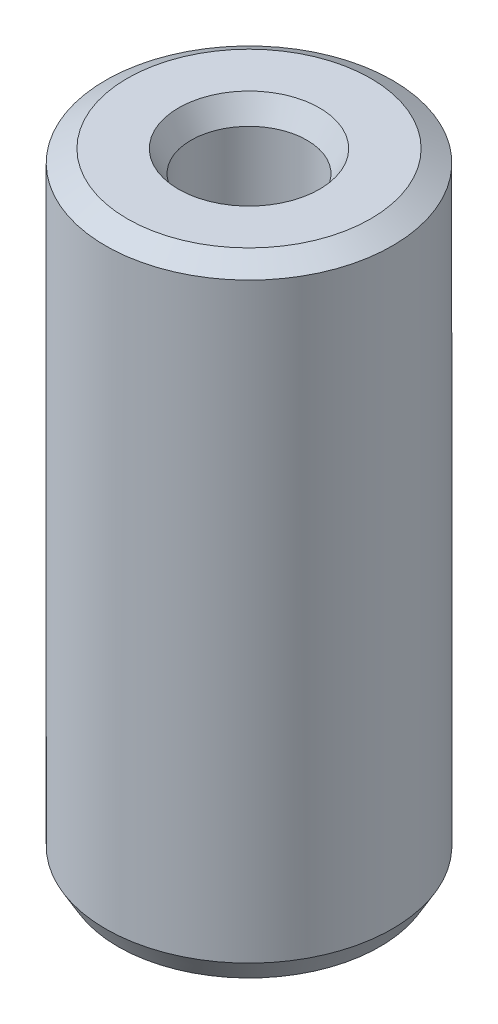
SolidWorks part; units mm, degrees
ref_plane "Front Plane" through (0, 0, 0) normal (0, 0, 1) x (1, 0, 0)
ref_plane "Top Plane" through (0, 0, 0) normal (0, 1, 0) x (1, 0, 0)
ref_plane "Right Plane" through (0, 0, 0) normal (1, 0, 0) x (0, 0, -1)
sketch "Sketch1" plane through (0, 0, 0) normal (0, 1, 0) x (1, 0, 0)
  circle A0 centre (0, 0) radius 45
  dimension "SLEEVE_OD" = 90
extrude "Boss-Extrude1" add sketch "Sketch1" along normal blind 196.344
sketch "Sketch2" plane through (0, 0, 0) normal (0, 1, 0) x (1, 0, 0)
  circle A0 centre (0, 0) radius 18.1924
  dimension "BORE_D" = 36.3849
extrude "Cut-Extrude1" cut sketch "Sketch2" along normal through all
chamfer "Chamfer1" distance 3.9336 angle 60 4 edges at (0, 196.344, 18.1924) (0, 0, 18.1924) (0, 0, 45) (0, 196.344, 45) first distance on face at (0, 196.344, 18.1924) first distance on face at (0, 0, 18.1924) first distance on face at (0, 196.344, 45)
